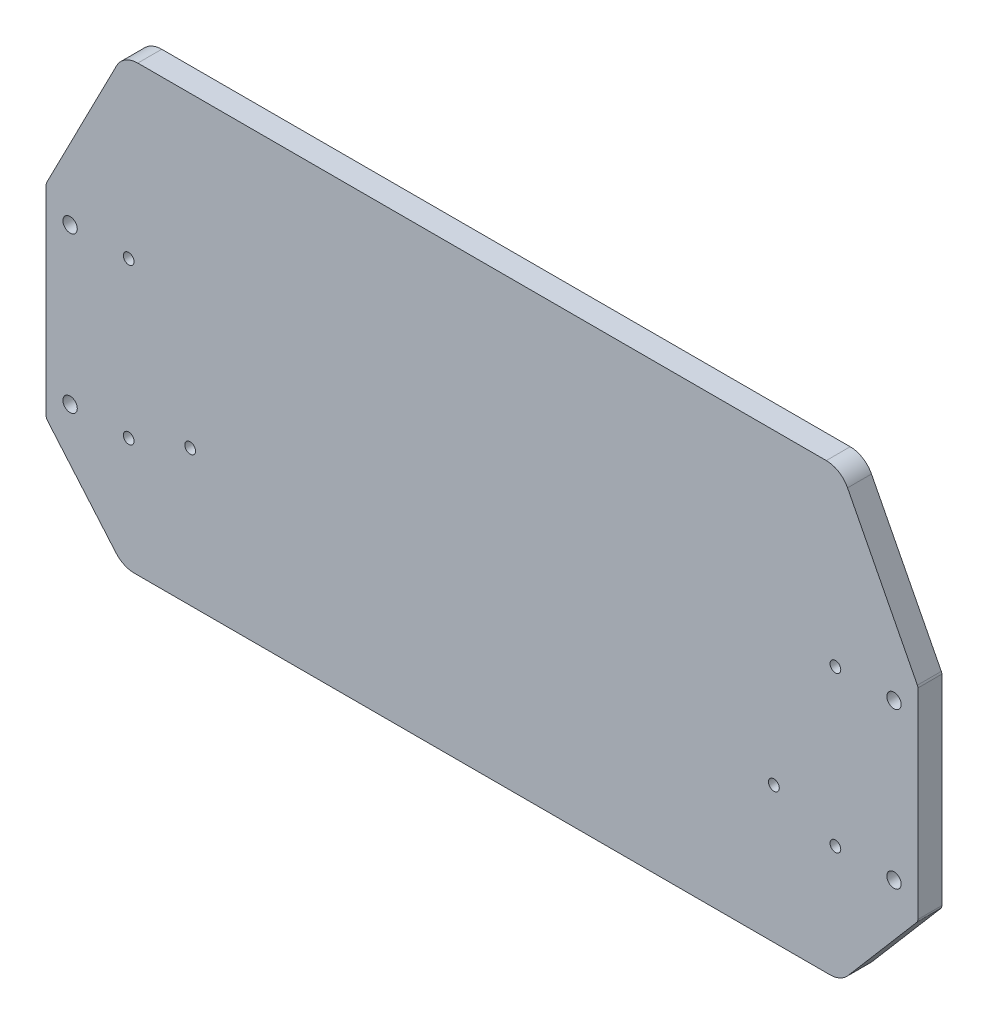
SolidWorks part; units mm, degrees
ref_plane "Plan de face" through (0, 0, 0) normal (0, 0, 1) x (1, 0, 0)
ref_plane "Plan de dessus" through (0, 0, 0) normal (0, 1, 0) x (1, 0, 0)
ref_plane "Plan de droite" through (0, 0, 0) normal (1, 0, 0) x (0, 0, -1)
sketch "Esquisse1" plane through (0, 0, 0) normal (0, 0, 1) x (1, 0, 0)
  line L0 (-182.2, 42.5) -> (-150, 105.2)
  line L1 (-182.2, 42.5) -> (182.2, 42.5)
  line L2 (-182.2, 42.5) -> (-182.2, -42.5)
  line L3 (-182.2, -42.5) -> (182.2, -42.5)
  line L4 (182.2, 42.5) -> (182.2, -42.5)
  line L5 (-150, 105.2) -> (150, 105.2)
  line L6 (-150, 105.2) -> (-150, 42.5)
  line L7 (-150, 42.5) -> (150, 42.5)
  line L8 (150, 105.2) -> (150, 42.5)
  line L9 (-150, -42.5) -> (150, -42.5)
  line L10 (-150, -42.5) -> (-150, -80.2)
  line L11 (-150, -80.2) -> (150, -80.2)
  line L12 (150, -42.5) -> (150, -80.2)
  line L13 (150, 105.2) -> (182.2, 42.5)
  line L14 (182.2, -42.5) -> (150, -80.2)
  line L15 (-150, -80.2) -> (-182.2, -42.5)
  dimension "D1" = 85
  dimension "D2" = 364.4
  dimension "D3" = 300
  dimension "D4" = 300
  dimension "D5" = 32.2
  dimension "D6" = 32.2
  dimension "D7" = 37.7
  dimension "D8" = 62.7
  dimension "D9" = 150
  dimension "D10" = 42.5
extrude "Boss.-Extru.1" add sketch "Esquisse1" along normal blind 10 contours L4 L1 L2 L3 | L8 L5 L6 L1 | L6 L0 L1 | L12 L3 L10 L11 | L15 L10 L3 | L13 L8 L1 | L14 L3 L12 region at (-160.7333, 63.4, 0) region at (0, 0, 0) region at (0, 73.85, 0) region at (-160.7333, -55.0667, 0) region at (160.7333, 63.4, 0) region at (0, -61.35, 0) region at (160.7333, -55.0667, 0)
sketch "Esquisse2" plane through (0, 0, 10) normal (0, 0, 1) x (1, 0, 0)
  line L1 (-182.2, 22.5) -> (-162.2, 22.5)
  line L2 (-182.2, 22.5) -> (-182.2, 42.5)
  line L3 (-182.2, 42.5) -> (-162.2, 42.5)
  line L4 (-162.2, 22.5) -> (-162.2, 42.5)
  line L5 (162.2, 22.5) -> (182.2, 22.5)
  line L6 (162.2, 22.5) -> (162.2, 42.5)
  line L7 (162.2, 42.5) -> (182.2, 42.5)
  line L8 (182.2, 22.5) -> (182.2, 42.5)
  line L9 (162.2, -22.5) -> (182.2, -22.5)
  line L10 (162.2, -22.5) -> (162.2, -42.5)
  line L11 (162.2, -42.5) -> (182.2, -42.5)
  line L12 (182.2, -22.5) -> (182.2, -42.5)
  line L13 (-182.2, -22.5) -> (-162.2, -22.5)
  line L14 (-182.2, -22.5) -> (-182.2, -42.5)
  line L15 (-182.2, -42.5) -> (-162.2, -42.5)
  line L16 (-162.2, -22.5) -> (-162.2, -42.5)
  line L17 (182.2, 42.5) -> (182.2, -42.5) construction
  line L18 (-182.2, 42.5) -> (-182.2, -42.5) construction
  dimension "D1" = 20
  dimension "D2" = 20
  dimension "D3" = 20
  dimension "D4" = 20
  dimension "D5" = 20
  dimension "D6" = 20
  dimension "D7" = 20
  dimension "D8" = 20
  dimension "D9" = 20
  dimension "D10" = 20
  dimension "D11" = 20
  dimension "D12" = 20
  dimension "D13" = 0
  dimension "D14" = 0
  dimension "D15" = 0
  dimension "D16" = 0
sketch "Esquisse3" plane through (0, 0, 10) normal (0, 0, 1) x (1, 0, 0)
  line L0 (-182.2, 42.5) -> (-162.2, 42.5) construction
  line L2 (-162.2, 22.5) -> (-162.2, 42.5) construction
  line L4 (-182.2, -22.5) -> (-162.2, -22.5) construction
  line L5 (-162.2, -22.5) -> (-162.2, -42.5) construction
  line L8 (162.2, -22.5) -> (182.2, -22.5) construction
  line L9 (162.2, -22.5) -> (162.2, -42.5) construction
  line L12 (162.2, 22.5) -> (162.2, 42.5) construction
  line L13 (162.2, 42.5) -> (182.2, 42.5) construction
  circle A0 centre (-147.7, 32.5) radius 2.25
  circle A1 centre (-172.2, 32.5) radius 3
  circle A3 centre (-172.2, -32.5) radius 3
  circle A4 centre (-147.7, -32.5) radius 2.25
  circle A6 centre (172.2, -32.5) radius 3
  circle A7 centre (147.7, -32.5) radius 2.25
  circle A9 centre (172.2, 32.5) radius 3
  circle A10 centre (147.7, 32.5) radius 2.25
  dimension "D1" = 6
  dimension "D5" = 4.5
  dimension "D10" = 6
  dimension "D13" = 4.5
  dimension "D14" = 14.5
  dimension "D17" = 14.5
  dimension "D19" = 6
  dimension "D27" = 4.5
  dimension "D28" = 4.5
  dimension "D30" = 6
  dimension "D15" = 14.5
  dimension "D7" = 14.5
  dimension "D2" = 10
  dimension "D3" = 10
  dimension "D4" = 10
  dimension "D11" = 10
  dimension "D12" = 10
  dimension "D16" = 10
  dimension "D20" = 10
  dimension "D21" = 10
  dimension "D26" = 10
  dimension "D31" = 10
  dimension "D32" = 10
  dimension "D33" = 10
extrude "Enlèv. mat.-Extru.1" cut sketch "Esquisse3" against normal blind 10
sketch "Esquisse4" plane through (0, 0, 10) normal (0, 0, 1) x (1, 0, 0)
  line L0 (-182.2, 42.5) -> (-182.2, -42.5) construction
  line L1 (-150, -80.2) -> (150, -80.2) construction
  line L2 (182.2, 42.5) -> (182.2, -42.5) construction
  circle A0 centre (-122, -23.2) radius 2.25
  circle A1 centre (122, -23.2) radius 2.25
  dimension "D1" = 4.5
  dimension "D2" = 4.5
  dimension "D3" = 60.2
  dimension "D4" = 57
  dimension "D5" = 57
  dimension "D6" = 60.2
extrude "Enlèv. mat.-Extru.2" cut sketch "Esquisse4" against normal blind 10
fillet "Congé1" radius 10 4 edges at (-150, 105.2, 5) (150, 105.2, 5) (150, -80.2, 5) (-150, -80.2, 5)
fillet "Congé2" radius 2 4 edges at (-182.2, -42.5, 5) (-182.2, 42.5, 5) (182.2, -42.5, 5) (182.2, 42.5, 5)
